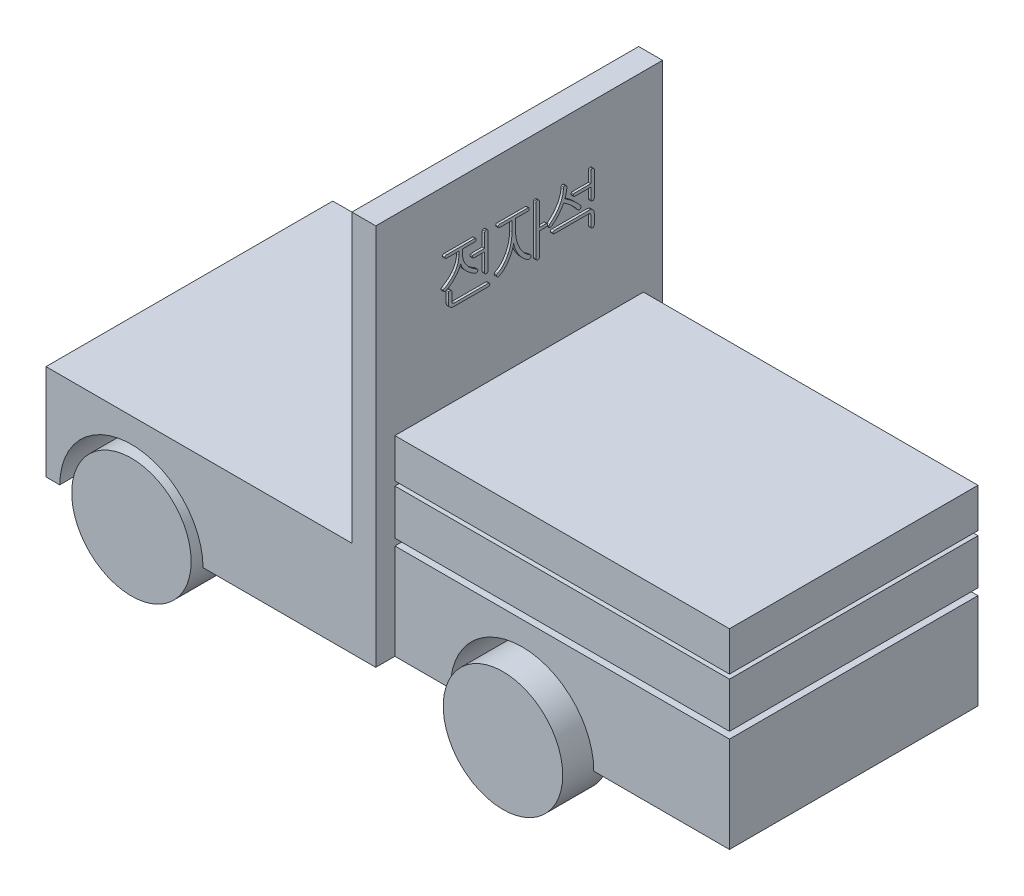
SolidWorks part; units mm, degrees
ref_plane "정면" through (0, 0, 0) normal (0, 0, 1) x (1, 0, 0)
ref_plane "윗면" through (0, 0, 0) normal (0, 1, 0) x (1, 0, 0)
ref_plane "우측면" through (0, 0, 0) normal (1, 0, 0) x (0, 0, -1)
sketch "스케치1" plane through (0, 0, 0) normal (0, 1, 0) x (1, 0, 0)
  line L1 (-139, 60) -> (139, 60)
  line L2 (-139, 60) -> (-139, -60)
  line L3 (-139, -60) -> (139, -60)
  line L4 (139, 60) -> (139, -60)
  line L5 (-139, 60) -> (139, -60) construction
  line L6 (-139, -60) -> (139, 60) construction
  point P0 (0, 0)
  dimension "D1" = 278
  dimension "D2" = 120
extrude "보스-돌출1" add sketch "스케치1" along normal blind 1
sketch "스케치2" plane through (0, 0, 0) normal (0, -1, 0) x (1, 0, 0)
  line L0 (-139, 0) -> (139, 0) construction
  line L1 (-139, -60) -> (-139, 60) construction
  line L2 (139, 60) -> (139, -60) construction
  line L3 (139, -52) -> (139, 52)
  line L4 (139, 52) -> (-1, 52)
  line L5 (139, -52) -> (-1, -52)
  line L6 (-1, 52) -> (-1, 60)
  line L7 (-139, 60) -> (139, 60) construction
  line L8 (-1, -52) -> (-1, -60)
  line L9 (-1, 60) -> (139, 60)
  line L10 (139, 60) -> (139, 52)
  line L11 (139, -52) -> (139, -60)
  line L12 (139, -60) -> (-1, -60)
  line M4 (139, -60) -> (139, 60)
  line M5 (139, 60) -> (-139, 60)
  line M7 (-139, -60) -> (139, -60)
  dimension "D1" = 104
  dimension "D2" = 140
extrude "컷-돌출1" cut sketch "스케치2" against normal blind 1 contours L6 L4 M4 M5 | L5 L8 M7 M4 region at (69, 0, 56) region at (69, 0, -56)
sketch "스케치4" plane through (0, 0, 0) normal (0, -1, 0) x (1, 0, 0)
  line L0 (-139, 60) -> (-139, -60)
  line L1 (-139, -60) -> (-1, -60)
  line L2 (-1, -60) -> (-1, -52)
  line L3 (-1, -52) -> (139, -52)
  line L4 (139, -52) -> (139, 52)
  line L5 (139, 52) -> (-1, 52)
  line L6 (-1, 52) -> (-1, 60)
  line L7 (-1, 60) -> (-139, 60)
extrude "보스-돌출2" add sketch "스케치4" along normal blind 1
extrude "보스-돌출3" add sketch "스케치4<2>" along normal blind 79
sketch "스케치4<2>" plane through (0, 0, 0) normal (0, -1, 0) x (1, 0, 0) same geometry as "스케치4"
sketch "스케치6" plane through (0, 0, -60) normal (0, 0, -1) x (-1, 0, 0)
  circle A0 centre (103.2598, -79.2996) radius 30
  circle A1 centre (-52.2178, -78.9182) radius 30
  dimension "D1" = 60
extrude "컷-돌출4" cut sketch "스케치6" against normal through all contours A1 | A0
sketch "스케치7" plane through (0, 0, -60) normal (0, 0, -1) x (-1, 0, 0)
  line L0 (1, 1) -> (1, -79) construction
  line L1 (139, 1) -> (1, 1)
  line L2 (139, 1) -> (139, -39)
  line L3 (139, -39) -> (1, -39)
  line L4 (1, 1) -> (1, -39)
  dimension "D1" = 40
extrude "컷-돌출5" cut sketch "스케치7" against normal through all
sketch "스케치8" plane through (0, 0, -52) normal (0, 0, -1) x (-1, 0, 0)
  line L0 (-139, 1) -> (-139, -79) construction
  line L1 (1, -39) -> (-139, -39)
  line L2 (1, -39) -> (1, -36.1864)
  line L3 (1, -36.1864) -> (-139, -36.1864)
  line L4 (-139, -39) -> (-139, -36.1864)
  line L5 (1, 1) -> (1, -39) construction
  line L6 (1, -15.4375) -> (-139, -15.4375)
  line L7 (1, -15.4375) -> (1, -17.2791)
  line L8 (1, -17.2791) -> (-139, -17.2791)
  line L9 (-139, -15.4375) -> (-139, -17.2791)
extrude "컷-돌출6" cut sketch "스케치8" against normal through all
sketch "스케치9" plane through (0, 0, -52) normal (0, 0, -1) x (-1, 0, 0)
  text T0 "배터리" font "Century Gothic" height in points 20
  text T1 "젯슨 나노" font "Century Gothic" height in points 20
sketch "스케치10" plane through (0, 0, -60) normal (0, 0, -1) x (-1, 0, 0)
  circle A0 centre (103.2598, -79.2996) radius 25
  circle A2 centre (-52.2178, -78.9182) radius 25
  point P0 (103.2598, -79.2996)
  point P4 (-52.2178, -78.9182)
extrude "보스-돌출4" add sketch "스케치10" against normal blind 20 separate body
sketch "스케치11" plane through (0, 0, 60) normal (0, 0, 1) x (1, 0, 0)
  circle A0 centre (-103.2598, -79.2996) radius 25
extrude "보스-돌출5" add sketch "스케치11" against normal blind 20 separate body
sketch "스케치12" plane through (0, 0, 60) normal (0, 0, 1) x (1, 0, 0)
  circle A0 centre (52.2178, -78.9182) radius 25
  point P0 (52.2178, -78.9182)
extrude "보스-돌출6" add sketch "스케치12" against normal blind 20 separate body
sketch "스케치13" plane through (0, 0, -40) normal (0, 0, 1) x (1, 0, 0)
  circle A0 centre (52.2178, -78.9182) radius 3
extrude "보스-돌출7" add sketch "스케치13" along normal blind 80
sketch "스케치14" plane through (0, 0, -40) normal (0, 0, 1) x (1, 0, 0)
  circle A0 centre (-103.2598, -79.2996) radius 3
extrude "보스-돌출8" add sketch "스케치14" along normal blind 80
sketch "스케치15" plane through (0, -39, 0) normal (0, 1, 0) x (1, 0, 0)
  line L0 (-1, -60) -> (-139, -60) construction
  line L1 (-1, 60) -> (-11, 60)
  line L2 (-1, 60) -> (-1, -60)
  line L3 (-1, -60) -> (-11, -60)
  line L4 (-11, 60) -> (-11, -60)
  dimension "D1" = 10
extrude "보스-돌출10" add sketch "스케치15" along normal blind 120
sketch "스케치16" plane through (-1, 0, 0) normal (1, 0, 0) x (0, 0, -1)
  text T0 "전자석" font "Century Gothic" height in points 72
extrude "보스-돌출11" add sketch "스케치16" along normal blind 1
extrude "보스-돌출12" add sketch "스케치9" along normal blind 1
